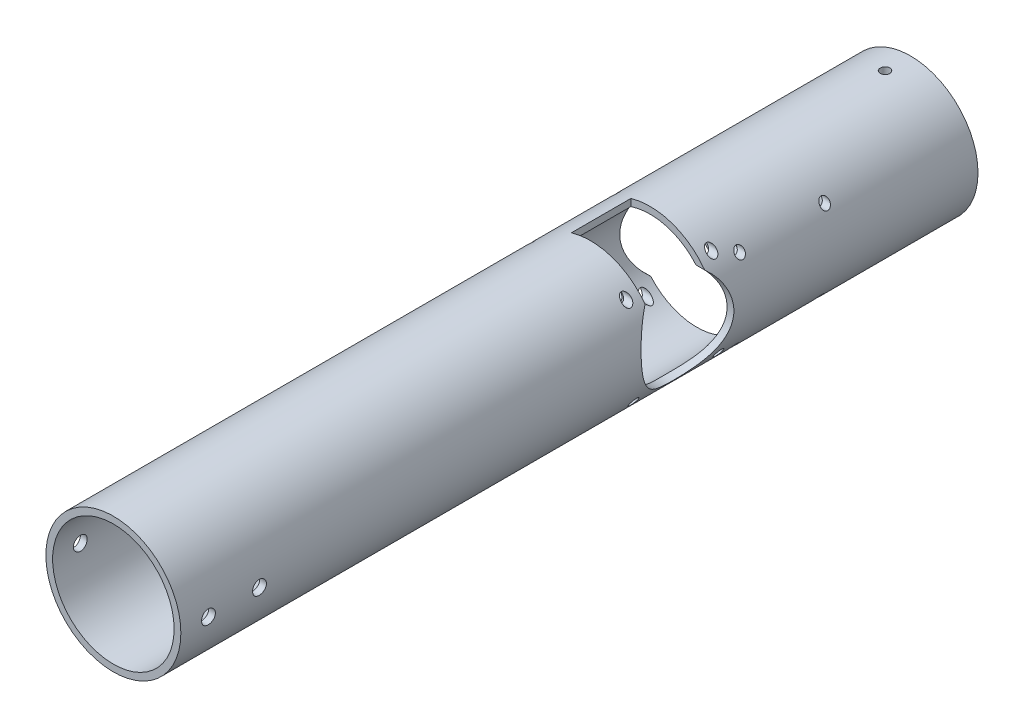
SolidWorks part; units mm, degrees
material "6061 Alloy"
ref_plane "Front Plane" through (0, 0, 0) normal (0, 0, 1) x (1, 0, 0)
ref_plane "Top Plane" through (0, 0, 0) normal (0, 1, 0) x (1, 0, 0)
ref_plane "Right Plane" through (0, 0, 0) normal (1, 0, 0) x (0, 0, -1)
sketch "Sketch1" plane through (0, 0, 0) normal (0, 0, 1) x (1, 0, 0)
  circle A0 centre (0, 0) radius 31.75
  circle A1 centre (0, 0) radius 28.575
  dimension "D1" = 63.5
  dimension "D2" = 57.15
extrude "Boss-Extrude1" add sketch "Sketch1" along normal blind 125 and the other way blind 250 contours A1 | A0 region at (0, 0, 0)
sketch "Sketch2" plane through (0, 0, 0) normal (1, 0, 0) x (0, 0, -1)
  circle A2 centre (163.488, -2) radius 21.75
  dimension "D1" = 43.5
  dimension "D2" = 163.488
  dimension "D3" = 2
extrude "Cut-Extrude1" cut sketch "Sketch2" against normal through all
sketch "Sketch3" plane through (0, 0, 0) normal (1, 0, 0) x (0, 0, -1)
  circle A1 centre (113.45, 2) radius 21.75
  dimension "D1" = 113.45
  dimension "D2" = 43.5
  dimension "D3" = 2
extrude "Cut-Extrude2" cut sketch "Sketch3" along normal through all
sketch "Sketch5" plane through (0, 0, 0) normal (1, 0, 0) x (0, 0, -1)
  line L1 (177.488, -12.75) -> (149.488, -12.75)
  line L2 (177.488, -12.75) -> (177.488, -34.75)
  line L3 (177.488, -34.75) -> (149.488, -34.75)
  line L4 (149.488, -12.75) -> (149.488, -34.75)
  line L5 (177.488, -12.75) -> (149.488, -34.75) construction
  line L6 (177.488, -34.75) -> (149.488, -12.75) construction
  circle A0 centre (163.488, -2) radius 21.75 construction
  circle A1 centre (163.488, -2) radius 21.75 construction
  point P0 (163.488, -23.75)
  dimension "D1" = 28
  dimension "D2" = 22
  dimension "D3" = 163.488
extrude "Cut-Extrude4" cut sketch "Sketch5" against normal through all from offset 9
sketch "Sketch6" plane through (0, 0, 0) normal (1, 0, 0) x (0, 0, -1)
  line L1 (99.45, 34.75) -> (127.45, 34.75)
  line L2 (99.45, 34.75) -> (99.45, 12.75)
  line L3 (99.45, 12.75) -> (127.45, 12.75)
  line L4 (127.45, 34.75) -> (127.45, 12.75)
  line L5 (99.45, 34.75) -> (127.45, 12.75) construction
  line L6 (99.45, 12.75) -> (127.45, 34.75) construction
  circle A0 centre (113.45, 2) radius 21.75 construction
  circle A1 centre (113.45, 2) radius 21.75 construction
  point P0 (113.45, 23.75)
  dimension "D1" = 28
  dimension "D2" = 22
  dimension "D3" = 113.45
extrude "Cut-Extrude5" cut sketch "Sketch6" along normal through all from offset 9 offset against normal yes
sketch "Sketch10" plane through (0, 0, 0) normal (1, 0, 0) x (0, 0, -1)
  line L1 (203.488, 38) -> (123.488, 38)
  line L2 (203.488, 38) -> (203.488, -42)
  line L3 (203.488, -42) -> (123.488, -42)
  line L4 (123.488, 38) -> (123.488, -42)
  line L5 (203.488, 38) -> (123.488, -42) construction
  line L6 (203.488, -42) -> (123.488, 38) construction
  point P0 (163.488, -2)
  dimension "D1" = 80
  dimension "D2" = 80
sketch "Sketch11" plane through (0, 0, 0) normal (1, 0, 0) x (0, 0, -1)
  line L0 (203.488, 38) -> (123.488, -42) construction
  line L1 (203.488, -42) -> (123.488, 38) construction
  circle A0 centre (183.488, 18) radius 2
  circle A1 centre (143.488, 18) radius 2
  circle A2 centre (143.488, -22) radius 2
  circle A3 centre (183.488, -22) radius 2
  dimension "D5" = 4
  dimension "D6" = 4
  dimension "D7" = 4
  dimension "D8" = 4
  dimension "D1" = 20
  dimension "D2" = 20
  dimension "D3" = 20
  dimension "D4" = 20
extrude "Cut-Extrude8" cut sketch "Sketch11" against normal through all both and the other way through all
sketch "Sketch12" plane through (0, 0, 0) normal (1, 0, 0) x (0, 0, -1)
  line L0 (-125, 31.75) -> (-125, -31.75) construction
  circle A0 centre (-112, 0) radius 3.25
  circle A1 centre (-88, 0) radius 3.25
  dimension "D1" = 6.5
  dimension "D2" = 6.5
  dimension "D3" = 24
  dimension "D4" = 13
extrude "Cut-Extrude10" cut sketch "Sketch12" against normal through all both and the other way through all
sketch "Sketch13" plane through (0, 0, 0) normal (0, 1, 0) x (1, 0, 0)
  line L0 (0, -34.925) -> (0, 34.925) construction
  line L1 (28.575, 250) -> (-28.575, 250) construction
  circle A0 centre (0, 238) radius 2.25
  dimension "D2" = 4.5
  dimension "D1" = 12
extrude "Cut-Extrude11" cut sketch "Sketch13" against normal through all both and the other way through all
sketch "Sketch14" plane through (0, 0, 0) normal (1, 0, 0) x (0, 0, -1)
  line L1 (88.45, 27) -> (138.45, 27)
  line L2 (88.45, 27) -> (88.45, -23)
  line L3 (88.45, -23) -> (138.45, -23)
  line L4 (138.45, 27) -> (138.45, -23)
  line L5 (88.45, 27) -> (138.45, -23) construction
  line L6 (88.45, -23) -> (138.45, 27) construction
  circle A0 centre (93.45, 22) radius 2
  circle A1 centre (133.45, 22) radius 2
  circle A2 centre (133.45, -18) radius 2
  circle A3 centre (93.45, -18) radius 2
  point P0 (113.45, 2)
  dimension "D4" = 4
  dimension "D5" = 4
  dimension "D6" = 4
  dimension "D7" = 4
  dimension "D1" = 50
  dimension "D2" = 50
  dimension "D3" = 20
  dimension "D8" = 20
  dimension "D9" = 20
  dimension "D10" = 20
sketch "Sketch15" plane through (0, 0, 0) normal (1, 0, 0) x (0, 0, -1)
  circle A0 centre (93.45, 22) radius 2
  circle A1 centre (133.45, 22) radius 2
  circle A2 centre (133.45, -18) radius 2
  circle A3 centre (93.45, -18) radius 2
extrude "Cut-Extrude12" cut sketch "Sketch15" against normal through all and the other way through all
hole_wizard "M4 Clearance Hole1" positions "Sketch18" profile "Sketch19" hole size "M4" standard "ANSI Metric" end condition through all
sketch "Sketch18" plane through (0, 0, 0) normal (1, 0, 0) x (0, 0, -1)
  circle A0 centre (93.45, 22) radius 2 construction
  circle A1 centre (133.45, 22) radius 2 construction
  circle A2 centre (93.45, -18) radius 2 construction
  circle A3 centre (133.45, -18) radius 2 construction
  point P0 (93.45, 22)
  point P2 (133.45, 22)
  point P4 (93.45, -18)
  point P6 (133.45, -18)
  point P20 (183.488, 18)
  point P23 (143.488, 18)
  point P26 (183.488, -22)
  point P29 (143.488, -22)
sketch "Sketch19" plane through (0, 22, -93.45) normal (0, 1, 0) x (0, 0, 1)
  line L0 (0, 0) -> (0, 31.75)
  line L1 (0, 31.75) -> (2.25, 31.75)
  line L2 (2.25, 31.75) -> (2.25, 0)
  line L5 (2.25, 0) -> (0, 0)
  line L11 (0, -6.35) -> (0, 107.95) construction
  dimension "Thru Hole Dia." = 4.5
  dimension "Thru Hole Depth" = 31.75
mirror "Mirror1" about plane through (0, 0, 0) normal (1, 0, 0) of "M4 Clearance Hole1"
